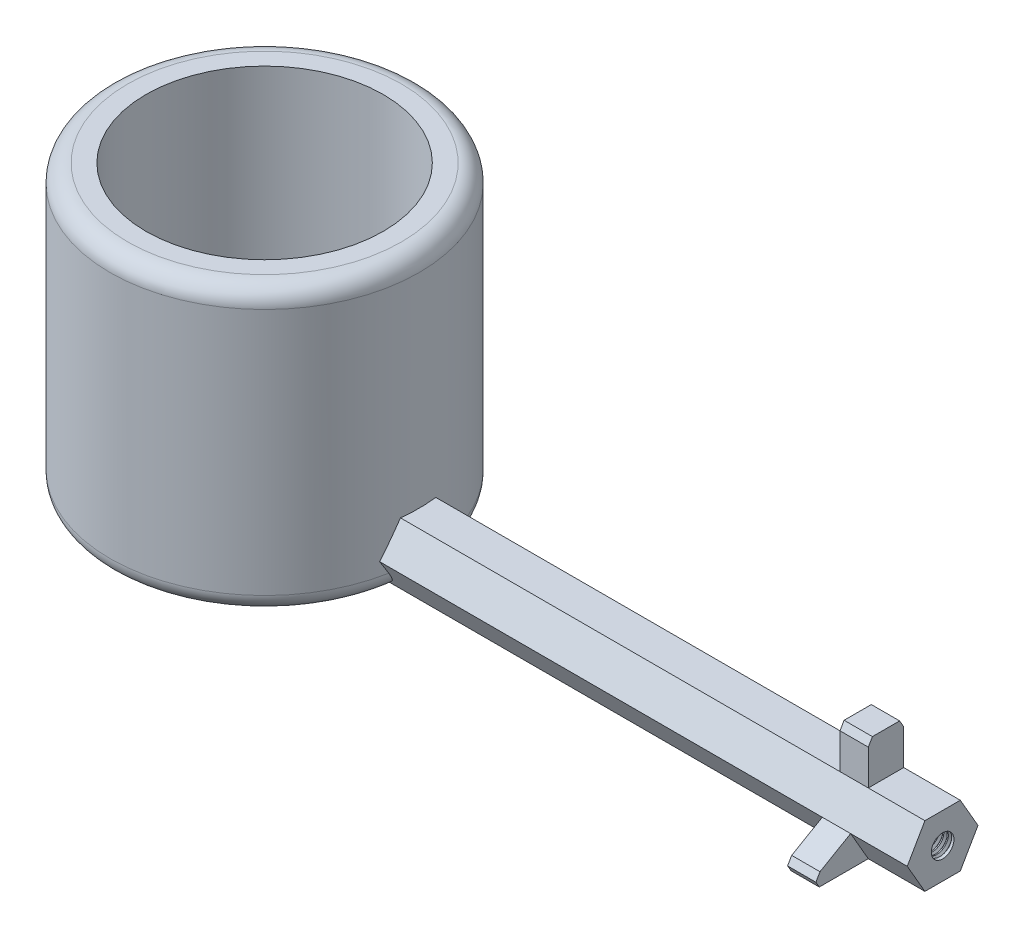
SolidWorks part; units mm, degrees
material "ABS"
ref_plane "Front Plane" through (0, 0, 0) normal (0, 0, 1) x (1, 0, 0)
ref_plane "Top Plane" through (0, 0, 0) normal (0, 1, 0) x (1, 0, 0)
ref_plane "Right Plane" through (0, 0, 0) normal (1, 0, 0) x (0, 0, -1)
sketch "Sketch1" plane through (0, 0, 0) normal (1, 0, 0) x (0, 0, -1)
  line L1 (2.5, 0) -> (1.25, 2.1651)
  line L2 (1.25, 2.1651) -> (-1.25, 2.1651)
  line L3 (-1.25, 2.1651) -> (-2.5, 0)
  line L4 (-2.5, 0) -> (-1.25, -2.1651)
  line L5 (-1.25, -2.1651) -> (1.25, -2.1651)
  line L6 (1.25, -2.1651) -> (2.5, 0)
  circle A0 centre (0, 0) radius 2.1651 construction
  dimension "D1" = 4.3301
extrude "Boss-Extrude1" add sketch "Sketch1" along normal blind 38
ref_plane "Plane1" through (0, -2.1651, 0) normal (0, -1, 0) x (-1, 0, 0)
sketch "Sketch2" plane through (0, -2.1651, 0) normal (0, -1, 0) x (-1, 0, 0)
  line L0 (0, 0) -> (9.906, 0) construction
  circle A0 centre (9.906, 0) radius 8.382
  circle A1 centre (9.906, 0) radius 10.922
  dimension "D1" = 16.764
  dimension "D3" = 9.906
  dimension "D2" = 21.844
extrude "Boss-Extrude2" add sketch "Sketch2" against normal blind 20
fillet "Fillet1" radius 1.25 3 edges at (-9.906, 17.8349, -10.922) (-9.906, -2.1651, -8.382) (-20.828, -2.1651, 0)
sketch "Sketch4" plane through (38, 0, 0) normal (1, 0, 0) x (0, 0, -1)
  circle A0 centre (0, 0) radius 1.53 construction
  dimension "D1" = 3.06
hole_wizard "Tap Drill for M2x0.4 Tap1" positions "Sketch8" profile "Sketch9" hole size "M2x0.4" standard "ANSI Metric"
sketch "Sketch8" plane through (38, 0, 0) normal (1, 0, 0) x (0, 0, -1)
  point P0 (0, 0)
sketch "Sketch9" plane through (38, 0, 0) normal (0, 1, 0) x (0, 0, -1)
  line L0 (0, 0) -> (0, 4)
  line L1 (0, 4) -> (0.8, 3.5193)
  line L2 (0.8, 3.5193) -> (0.8, 0)
  line L5 (0.8, 0) -> (0, 0)
  line L10 (0, 4) -> (-0.8, 3.5193) construction
  line L11 (0, -6.35) -> (0, 107.95) construction
  dimension "Hole Dia." = 1.6
  dimension "Hole Depth" = 4
  dimension "Drill Angle" = 118
thread "Thread1" pitch 0.3175 method cut profile "Thread Profile1" start angle 0, offset 0, length 5.2, pitch 0.3175, diameter 1.6
ref_plane "Plane2" through (38, 0, 0.8) normal (0, -1, 0) x (0, 0, 1)
sketch "Thread Profile1" plane through (38, 0, 0.8) normal (0, -1, 0) x (0, 0, 1)
  line L0 (0, 0) -> (0, 0.3175) construction
  line L1 (0, 0) -> (0.1719, 0.0992)
  line L2 (0.1719, 0.0992) -> (0.1719, 0.1389)
  line L3 (0.1719, 0.1389) -> (0, 0.2381)
  line L4 (0.1719, 0.1191) -> (0, 0.1191) construction
  line L11 (0, 0) -> (0, 0.2381)
  point P2 (0, 0)
  dimension "Pitch" = 0.3175
  dimension "Profile_Angle" = 60
  dimension "Profile_Land" = 0.0397
  dimension "Profile_Height" = 0.1719
sketch "Sketch10" plane through (0, 2.1651, 0) normal (0, 1, 0) x (1, 0, 0)
  line L0 (38, 0) -> (34, 0) construction
  line L1 (38, 1.25) -> (38, -1.25) construction
  line L2 (38, 1.25) -> (0.9442, 1.25) construction
  line L3 (34, 1.25) -> (32, 1.25)
  line L4 (34, 1.25) -> (34, -1.25)
  line L5 (34, -1.25) -> (32, -1.25)
  line L6 (32, 1.25) -> (32, -1.25)
  line L7 (38, -1.25) -> (0.9442, -1.25) construction
  dimension "D1" = 4
  dimension "D2" = 2
  dimension "D3" = 6
extrude "Boss-Extrude3" add sketch "Sketch10" along normal blind 3
pattern_circular "CirPattern2" count 6 over 360 about axis through (34.4807, 0, 0) along (1, 0, 0) skipping 1, 3, 5 of "Boss-Extrude3"
chamfer "Chamfer3" distance 3 angle 30 2 edges at (33, -3.6651, -3.8481) (33, -3.6651, 3.8481) first distance on face at (33, -2.9151, -2.549) first distance on face at (33, -2.9151, 2.549)
chamfer "Chamfer4" distance 0.5 angle 30 4 edges at (33, -1.5, -5.0981) (33, 5.1651, -1.25) (33, 5.1651, 1.25) (33, -1.5, 5.0981) first distance on face at (33, -0.75, -3.799) first distance on face at (33, 3.6651, -1.25) first distance on face at (33, 3.6651, 1.25) first distance on face at (33, -0.75, 3.799)
